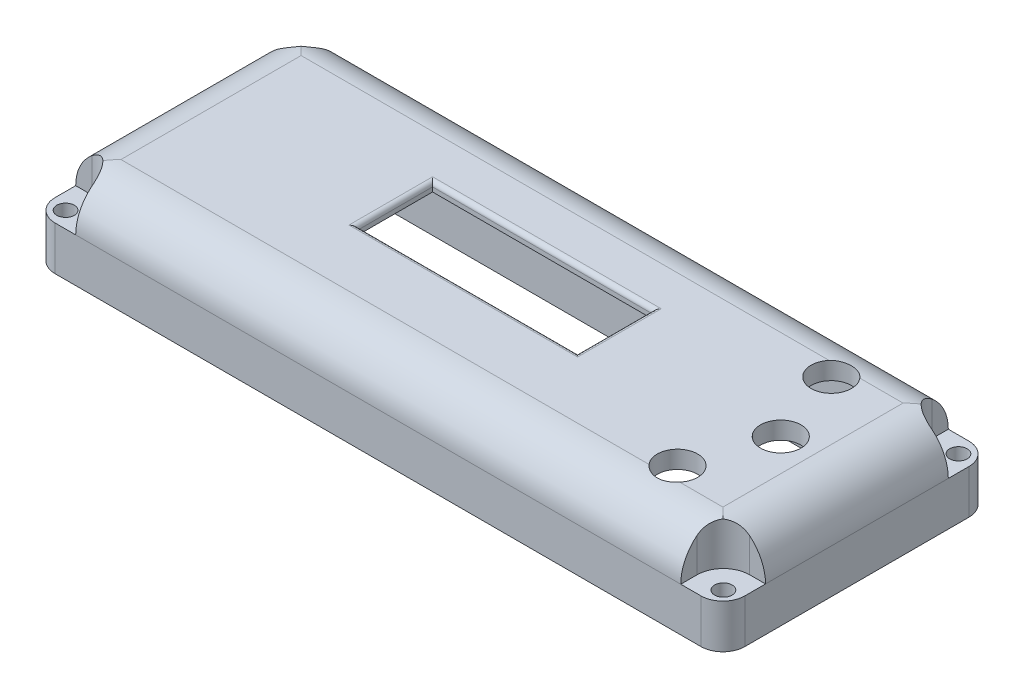
SolidWorks part; units mm, degrees
ref_plane "Спереди" through (0, 0, 0) normal (0, 0, 1) x (1, 0, 0)
ref_plane "Сверху" through (0, 0, 0) normal (0, 1, 0) x (1, 0, 0)
ref_plane "Справа" through (0, 0, 0) normal (1, 0, 0) x (0, 0, -1)
sketch "основной эскиз" plane through (0, 0, 0) normal (0, 1, 0) x (1, 0, 0)
  line L0 (-39.25, 12.75) -> (-39.25, -12.75)
  line L1 (9.1949, -1.7365) -> (9.1949, 3.7835) construction
  line L2 (-12.8222, -1.7365) -> (9.1949, -1.7365) construction
  line L3 (9.1949, 3.7835) -> (-12.8222, 3.7835) construction
  line L4 (-12.8222, 3.7835) -> (-12.8222, -1.7365) construction
  line L5 (33.9689, 12) -> (-33.9689, 12)
  line L6 (-36, 9.9689) -> (-36, -9.9689)
  line L7 (-33.9689, -12) -> (33.9689, -12)
  line L8 (36, -9.9689) -> (36, 9.9689)
  line L9 (36.75, -15.25) -> (-36.75, -15.25)
  line L10 (39.25, -12.75) -> (39.25, 12.75)
  line L11 (36.75, 15.25) -> (-36.75, 15.25)
  line L12 (34.6459, 13) -> (-34.6459, 13)
  line L13 (-37, 10.6459) -> (-37, -10.6459)
  line L14 (-34.6459, -13) -> (34.6459, -13)
  line L15 (37, -10.6459) -> (37, 10.6459)
  line L16 (9.1949, -1.7365) -> (9.1949, 3.7835)
  line L17 (-12.8222, -1.7365) -> (9.1949, -1.7365)
  line L18 (9.1949, 3.7835) -> (-12.8222, 3.7835)
  line L19 (-12.8222, 3.7835) -> (-12.8222, -1.7365)
  line L27 (18.0778, 5.9435) -> (18.0778, -6.0565) construction
  line L32 (10.6949, 5.2835) -> (-14.3222, 5.2835)
  line L33 (-14.3222, 5.2835) -> (-14.3222, -3.2365)
  line L34 (-14.3222, -3.2365) -> (10.6949, -3.2365)
  line L35 (10.6949, -3.2365) -> (10.6949, 5.2835)
  line L36 (-19.9222, -6.0565) -> (-19.9222, 5.9435) construction
  line L38 (-19.9222, -6.0565) -> (18.0778, -6.0565)
  line L39 (18.0778, 5.9435) -> (-19.9222, 5.9435)
  line L40 (-19.9222, -6.0565) -> (-19.9222, 5.9435)
  line L41 (-20.9222, -7.0565) -> (19.0778, -7.0565)
  line L42 (19.0778, 6.9435) -> (19.0778, -7.0565)
  line L43 (19.0778, 6.9435) -> (-20.9222, 6.9435)
  line L44 (-20.9222, -7.0565) -> (-20.9222, 6.9435)
  line L45 (18.0778, 5.9435) -> (18.0778, -6.0565)
  circle A0 centre (37.4542, -13.4) radius 1
  circle A1 centre (-37.4, 13.4) radius 1
  circle A2 centre (37.4, 13.4) radius 1
  arc A3 (-39.25, -12.75) -> (-36.75, -15.25) centre (-36.75, -12.75) ccw
  circle A4 centre (-37.4, -13.4) radius 1
  arc A5 (-36, 9.9689) -> (-33.9689, 12) centre (-38, 14) ccw
  circle A6 centre (27.5845, -8.7501) radius 1.8 construction
  circle A7 centre (30.5845, -0.0001) radius 1.8 construction
  circle A8 centre (27.5845, 8.7499) radius 1.8 construction
  circle A9 centre (27.5845, -8.7501) radius 1.8
  arc A10 (-36.75, 15.25) -> (-39.25, 12.75) centre (-36.75, 12.75) ccw
  arc A11 (-33.9689, -12) -> (-36, -9.9689) centre (-38, -14) ccw
  arc A12 (36, -9.9689) -> (33.9689, -12) centre (38, -14) ccw
  arc A13 (33.9689, 12) -> (36, 9.9689) centre (38, 14) ccw
  arc A14 (36.75, -15.25) -> (39.25, -12.75) centre (36.75, -12.75) ccw
  arc A15 (39.25, 12.75) -> (36.75, 15.25) centre (36.75, 12.75) ccw
  arc A16 (-37, 10.6459) -> (-34.6459, 13) centre (-38, 14) ccw
  arc A17 (-34.6459, -13) -> (-37, -10.6459) centre (-38, -14) ccw
  arc A18 (37, -10.6459) -> (34.6459, -13) centre (38, -14) ccw
  arc A19 (34.6459, 13) -> (37, 10.6459) centre (38, 14) ccw
  circle A20 centre (30.5845, -0.0001) radius 1.8
  circle A21 centre (27.5845, 8.7499) radius 1.8
  circle A22 centre (27.5845, 8.7499) radius 2.3
  circle A23 centre (30.5845, -0.0001) radius 2.3
  circle A24 centre (27.5845, -8.7501) radius 2.3
  dimension "D4" = 2
  dimension "D1" = 1.5
  dimension "D2" = 1
  dimension "D3" = 0.5
extrude "Бобышка поверхности корпуса" add sketch "основной эскиз" along normal blind 10 contours L11 A10 L0 A3 L9 A14 L10 A15
extrude "Вырез основной внутри корпуса" cut sketch "Эскиз1<3>" along normal blind 8 contours L7 A12 L8 A13 L5 A5 L6 A11
sketch "Эскиз1<3>" plane through (0, 0, 0) normal (0, 1, 0) x (1, 0, 0) same geometry as "основной эскиз"
extrude "Бобышка зажима платы" add sketch "Эскиз1<4>" against normal blind 2 contours L14 A18 L15 A19 L12 A16 L13 A17
sketch "Эскиз1<4>" plane through (0, 0, 0) normal (0, 1, 0) x (1, 0, 0) same geometry as "основной эскиз"
extrude "Вырез вспомогательный зажима платы" cut sketch "Эскиз1<6>" against normal blind 2 and the other way blind 2 contours L7 A12 L8 A13 L5 A5 L6 A11
sketch "Эскиз1<6>" plane through (0, 0, 0) normal (0, 1, 0) x (1, 0, 0) same geometry as "основной эскиз"
extrude "Вырез под болты крепления" cut sketch "Эскиз1<7>" against normal through all and the other way through all contours A0 | A2 | A1 | A4
sketch "Эскиз1<7>" plane through (0, 0, 0) normal (0, 1, 0) x (1, 0, 0) same geometry as "основной эскиз"
sketch "Эскиз  вспомгательный под USB" plane through (-37, 0, 0) normal (-1, 0, 0) x (0, 0, 1)
  line L0 (-10.6459, -2) -> (10.6459, -2) construction
  line L1 (-5, 0) -> (5, 0)
  line L2 (-5, 0) -> (-5, -2)
  line L3 (-5, -2) -> (5, -2)
  line L4 (5, 0) -> (5, -2)
  line L5 (-5, 0) -> (5, -2) construction
  line L6 (-5, -2) -> (5, 0) construction
  point P0 (0, -1)
  dimension "D1" = 15.25
  dimension "D2" = 15.25
extrude "Вырез вспомгательный под USB" cut sketch "Эскиз  вспомгательный под USB" against normal up to next contours L4 L3 L2 L1
sketch "Эскиз3" plane through (0, 10, 0) normal (0, 1, 0) x (1, 0, 0)
  line L0 (39.25, -12.75) -> (39.25, 12.75) construction
  line L1 (36.75, -15.25) -> (-36.75, -15.25) construction
  line L2 (-39.25, 12.75) -> (-39.25, -12.75) construction
  line L3 (36.75, 15.25) -> (-36.75, 15.25) construction
  line L4 (39.25, -12.75) -> (39.25, 12.75)
  line L5 (36.75, -15.25) -> (-36.75, -15.25)
  line L6 (-39.25, 12.75) -> (-39.25, -12.75)
  line L7 (36.75, 15.25) -> (-36.75, 15.25)
  line L8 (-34.4, 13.4) -> (-34.4, 15.25)
  line L9 (-37.4, 10.4) -> (-39.25, 10.4)
  line L10 (-37.4, -10.4) -> (-39.25, -10.4)
  line L11 (-34.4, -13.4) -> (-34.4, -15.25)
  line L12 (37.4542, -10.4) -> (39.25, -10.4)
  line L13 (34.4542, -13.4) -> (34.4542, -15.25)
  line L14 (34.4, 13.4) -> (34.4, 15.25)
  line L15 (37.4, 10.4) -> (39.25, 10.4)
  arc A0 (39.25, 12.75) -> (36.75, 15.25) centre (36.75, 12.75) ccw construction
  circle A1 centre (37.4, 13.4) radius 1 construction
  circle A2 centre (37.4542, -13.4) radius 1 construction
  arc A3 (36.75, -15.25) -> (39.25, -12.75) centre (36.75, -12.75) ccw construction
  arc A4 (-39.25, -12.75) -> (-36.75, -15.25) centre (-36.75, -12.75) ccw construction
  circle A5 centre (-37.4, -13.4) radius 1 construction
  arc A6 (-36.75, 15.25) -> (-39.25, 12.75) centre (-36.75, 12.75) ccw construction
  circle A7 centre (-37.4, 13.4) radius 1 construction
  arc A8 (39.25, 12.75) -> (36.75, 15.25) centre (36.75, 12.75) ccw
  circle A9 centre (37.4, 13.4) radius 1
  circle A10 centre (37.4542, -13.4) radius 1
  arc A11 (36.75, -15.25) -> (39.25, -12.75) centre (36.75, -12.75) ccw
  arc A12 (-39.25, -12.75) -> (-36.75, -15.25) centre (-36.75, -12.75) ccw
  circle A13 centre (-37.4, -13.4) radius 1
  arc A14 (-36.75, 15.25) -> (-39.25, 12.75) centre (-36.75, 12.75) ccw
  circle A15 centre (-37.4, 13.4) radius 1
  arc A16 (-37.4, 10.4) -> (-34.4, 13.4) centre (-37.4, 13.4) ccw
  arc A17 (34.4, 13.4) -> (37.4, 10.4) centre (37.4, 13.4) ccw
  arc A18 (37.4542, -10.4) -> (34.4542, -13.4) centre (37.4542, -13.4) ccw
  arc A19 (-34.4, -13.4) -> (-37.4, -10.4) centre (-37.4, -13.4) ccw
  circle M1 centre (37.4, 13.4) radius 1
  circle M2 centre (-37.4, 13.4) radius 1
  circle M3 centre (-37.4, -13.4) radius 1
  circle M4 centre (37.4542, -13.4) radius 1
  arc M5 (39.25, 12.75) -> (36.75, 15.25) centre (36.75, 12.75) ccw
  line M6 (36.75, 15.25) -> (-36.75, 15.25)
  arc M7 (-36.75, 15.25) -> (-39.25, 12.75) centre (-36.75, 12.75) ccw
  line M8 (-39.25, 12.75) -> (-39.25, -12.75)
  arc M9 (-39.25, -12.75) -> (-36.75, -15.25) centre (-36.75, -12.75) ccw
  line M10 (-36.75, -15.25) -> (36.75, -15.25)
  arc M11 (36.75, -15.25) -> (39.25, -12.75) centre (36.75, -12.75) ccw
  line M12 (39.25, -12.75) -> (39.25, 12.75)
  dimension "D1" = 6
  dimension "D2" = 1.85
  dimension "D3" = 1.85
extrude "Вырез под шляпки болтов крепления" cut sketch "Эскиз3" against normal blind 5 contours L9 A16 L8 L7 M7 M8 M2 | L11 A19 L10 M8 M9 M10 M3 | L12 A18 L13 M10 M11 M12 M4 | L14 A17 L15 M12 M5 M6 M1 region at (38.4695, 10, 14.4695) region at (38.325, 10, -10.4686) region at (-35.575, 10, 15.1814) region at (-34.4686, 10, -14.325)
fillet "Скругление корпуса" radius 5 4 edges at (-39.25, 10, 0) (39.25, 10, 0) (0, 10, -15.25) (0.0271, 10, 15.25)
extrude "Вырез под экран" cut sketch "основной эскиз<8>" against normal through all both and the other way through all contours L32 L33 L34 L35
sketch "основной эскиз<8>" plane through (0, 0, 0) normal (0, 1, 0) x (1, 0, 0) same geometry as "основной эскиз"
extrude "Вырез под дисплей" cut sketch "основной эскиз<11>" along normal blind 9 contours L41 L42 L43 L44
sketch "основной эскиз<11>" plane through (0, 0, 0) normal (0, 1, 0) x (1, 0, 0) same geometry as "основной эскиз"
fillet "Скругление по экран" radius 0.5 4 edges at (10.6949, 10, -1.0235) (-1.8136, 10, 3.2365) (-14.3222, 10, -1.0235) (-1.8136, 10, -5.2835)
sketch "Эскиз выреза под USB" plane through (-39.25, 0, 0) normal (-1, 0, 0) x (0, 0, 1)
  line L0 (-12.75, 0) -> (12.75, 0) construction
  line L1 (-4.125, -0.7) -> (4.125, -0.7)
  line L2 (-4.125, -0.7) -> (-4.125, 0)
  line L3 (-3.6351, 0.8) -> (3.6351, 0.8)
  line L4 (4.125, -0.7) -> (4.125, 0)
  line L5 (-4.125, -0.7) -> (4.125, 0.7) construction
  line L6 (-4.125, 0.7) -> (4.125, -0.7) construction
  line L7 (-4.125, 0) -> (4.125, 0)
  line L8 (-4.125, 0) -> (-3.6351, 0.8)
  line L9 (4.125, 0) -> (3.6351, 0.8)
  point P0 (0, 0)
  dimension "D1" = 15.25
  dimension "D2" = 8.25
  dimension "D3" = 0.8
  dimension "D4" = 0.5
  dimension "D5" = 0.5
extrude "Вырез-Вытянуть12" cut sketch "Эскиз выреза под USB" against normal up to next contours L2 L8 L3 L9 L4 L1
fillet "Скругление под вырез USB" radius 1 2 edges at (-37.625, 0.8, 3.6351) (-37.625, 0.8, -3.6351)
extrude "Вырез под кнопки" cut sketch "основной эскиз<13>" against normal through all both and the other way through all contours A22 | A23 | A24
sketch "основной эскиз<13>" plane through (0, 0, 0) normal (0, 1, 0) x (1, 0, 0) same geometry as "основной эскиз"
